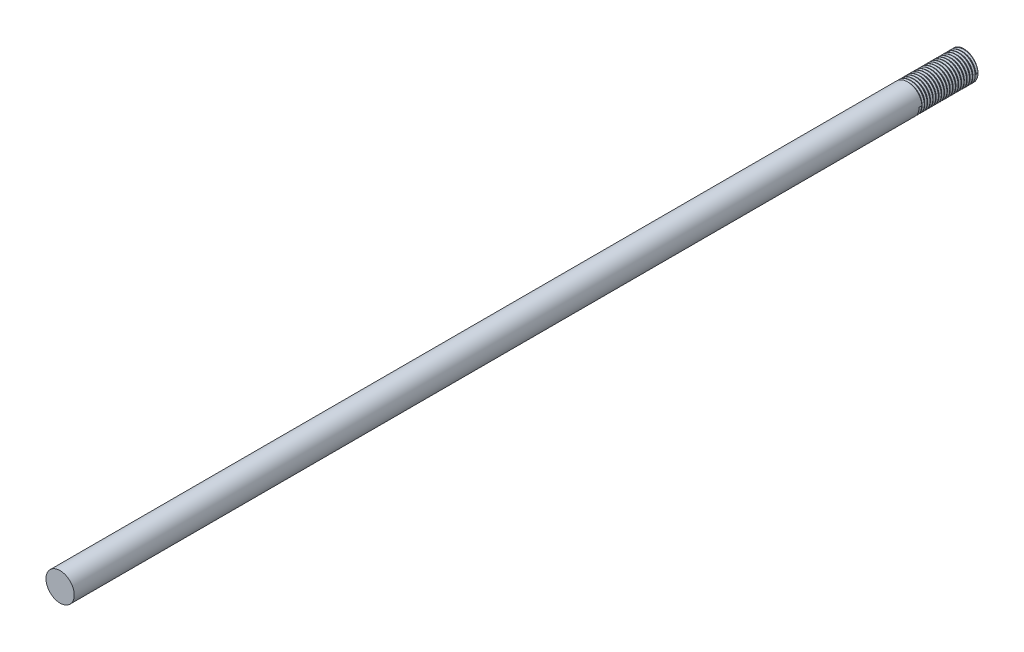
SolidWorks part; units mm, degrees
ref_plane "Front Plane" through (0, 0, 0) normal (0, 0, 1) x (1, 0, 0)
ref_plane "Top Plane" through (0, 0, 0) normal (0, 1, 0) x (1, 0, 0)
ref_plane "Right Plane" through (0, 0, 0) normal (1, 0, 0) x (0, 0, -1)
sketch "Sketch2" plane through (0, 0, 0) normal (0, 0, 1) x (1, 0, 0)
  circle A0 centre (0, 0) radius 5
  dimension "D1" = 10
extrude "Boss-Extrude1" add sketch "Sketch2" along normal blind 320
thread "Thread1" pitch 1 method cut profile "Thread Profile2" start angle 0, offset 0, length 20, pitch 1, diameter 10
ref_plane "Plane2" through (5, 0, 0) normal (0, -1, 0) x (1, 0, 0)
sketch "Thread Profile2" plane through (5, 0, 0) normal (0, -1, 0) x (1, 0, 0)
  line L0 (0, 0) -> (0, 1) construction
  line L11 (0, 0) -> (0, 0.875)
  line L12 (0, 0.875) -> (-0.5413, 0.5625)
  line L13 (-0.5413, 0.5625) -> (-0.5413, 0.3125)
  line L15 (-0.5413, 0.3125) -> (0, 0)
  line L17 (-0.5413, 0.4375) -> (0, 0.4375) construction
  point P2 (0, 0)
  dimension "Pitch" = 1
  dimension "Profile_Angle" = 60
  dimension "Profile_Land" = 0.25
  dimension "Profile_Height" = 0.5413
